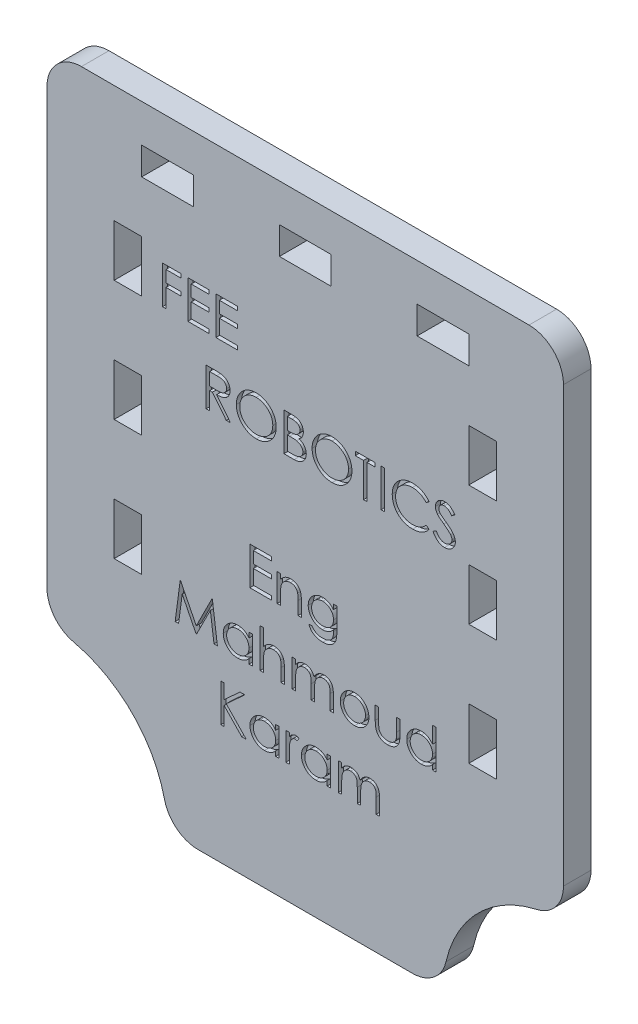
SolidWorks part; units mm, degrees
material "Beech"
ref_plane "Front" through (0, 0, 0) normal (0, 0, 1) x (1, 0, 0)
ref_plane "Top" through (0, 0, 0) normal (0, 1, 0) x (1, 0, 0)
ref_plane "Right" through (0, 0, 0) normal (1, 0, 0) x (0, 0, -1)
sketch "Sketch1" plane through (0, 0, 0) normal (0, 0, 1) x (1, 0, 0)
  line L0 (75, -55) -> (-75, -55) construction
  line L1 (-75, -90) -> (75, -90) construction
  line L2 (-75, -90) -> (-75, 90) construction
  line L3 (-75, 90) -> (75, 90) construction
  line L4 (75, -90) -> (75, 90) construction
  line L5 (-75, -90) -> (75, 90) construction
  line L6 (-75, 90) -> (75, -90) construction
  line L7 (-65, 90) -> (65, 90)
  line L8 (31.1252, -90) -> (-31.1252, -90)
  line L9 (75, -46.1252) -> (75, 80) construction
  line L10 (65, 90) -> (-65, 90) construction
  line L12 (-31.1252, -90) -> (31.1252, -90) construction
  line L17 (75, 80) -> (75, -46.1252)
  line L20 (-75, -46.1252) -> (-75, 80)
  arc A0 (-67.2222, -55.8751) -> (-40.8751, -82.2222) centre (-75, -90) cw
  arc A1 (67.2222, -55.8751) -> (40.8751, -82.2222) centre (75, -90) ccw
  arc A2 (-31.1252, -90) -> (-40.8751, -82.2222) centre (-31.1252, -80) cw
  arc A3 (-67.2222, -55.8751) -> (-75, -46.1252) centre (-65, -46.1252) cw
  arc A4 (40.8751, -82.2222) -> (31.1252, -90) centre (31.1252, -80) cw
  arc A5 (75, 80) -> (65, 90) centre (65, 80) ccw
  arc A6 (-65, 90) -> (-75, 80) centre (-65, 80) ccw
  arc A7 (75, -46.1252) -> (67.2222, -55.8751) centre (65, -46.1252) cw
  point P0 (0, 0)
  dimension "D6" = 35
  dimension "D8" = 10
  dimension "D5" = 10
  dimension "D1" = 126.1252
  dimension "D2" = 150
  dimension "D4" = 35
extrude "Boss-Extrude1" add sketch "Sketch1" along normal blind 8 contours A1 L9 L10 A0 L12 region at (0, 5.8065, 0)
sketch "Sketch2" plane through (0, 0, 8) normal (0, 0, 1) x (1, 0, 0)
  text T0 "FEE\r\n   ROBOTICS\r\n \r\n      Eng\r\n Mahmoud\r\n    Karam" font "Century Gothic" height 11
extrude "Cut-Extrude1" cut sketch "Sketch2" against normal blind 1.5
sketch "Sketch4" plane through (0, 0, 8) normal (0, 0, 1) x (1, 0, 0)
  line L0 (7.5, 71) -> (-7.5, 71)
  line L1 (-47.5, 79) -> (-32.5, 79)
  line L2 (-47.5, 79) -> (-47.5, 71)
  line L3 (-47.5, 71) -> (-32.5, 71)
  line L4 (-32.5, 79) -> (-32.5, 71)
  line L5 (-47.5, 79) -> (-32.5, 71) construction
  line L6 (-47.5, 71) -> (-32.5, 79) construction
  line L7 (-7.5, 71) -> (-7.5, 79)
  line L8 (-7.5, 79) -> (7.5, 79)
  line L9 (0, 79) -> (0, 71) construction
  line L10 (-65, 90) -> (65, 90) construction
  line L11 (47.5, 79) -> (32.5, 79)
  line L12 (47.5, 79) -> (47.5, 71)
  line L13 (47.5, 71) -> (32.5, 71)
  line L14 (32.5, 79) -> (32.5, 71)
  line L15 (7.5, 71) -> (7.5, 79)
  point P4 (-40, 75)
  dimension "D1" = 15
  dimension "D2" = 8
  dimension "D3" = 7.5
  dimension "D4" = 11
  dimension "D5" = 25
extrude "Cut-Extrude2" cut sketch "Sketch4" against normal through all
sketch "Sketch5" plane through (0, 0, 8) normal (0, 0, 1) x (1, 0, 0)
  line L0 (0, 0) -> (0, 12.759) construction
  line L1 (-47.5, 56) -> (-55.5, 56)
  line L2 (-47.5, 56) -> (-47.5, 41)
  line L3 (-47.5, 41) -> (-55.5, 41)
  line L4 (-55.5, 56) -> (-55.5, 41)
  line L5 (-47.5, 56) -> (-55.5, 41) construction
  line L6 (-47.5, 41) -> (-55.5, 56) construction
  line L7 (-47.5, 71) -> (-32.5, 71) construction
  line L8 (-47.5, 79) -> (-47.5, 71) construction
  line L9 (-47.5, 6) -> (-55.5, 6)
  line L10 (-55.5, 21) -> (-55.5, 6)
  line L11 (-47.5, 21) -> (-55.5, 21)
  line L12 (-47.5, 21) -> (-47.5, 6)
  line L13 (-47.5, -29) -> (-55.5, -29)
  line L14 (-55.5, -14) -> (-55.5, -29)
  line L15 (-47.5, -14) -> (-55.5, -14)
  line L16 (-47.5, -14) -> (-47.5, -29)
  line L17 (47.5, 41) -> (55.5, 41)
  line L18 (55.5, 56) -> (55.5, 41)
  line L19 (47.5, 56) -> (55.5, 56)
  line L20 (47.5, 56) -> (47.5, 41)
  line L21 (47.5, -14) -> (47.5, -29)
  line L22 (47.5, -14) -> (55.5, -14)
  line L23 (55.5, -14) -> (55.5, -29)
  line L24 (47.5, -29) -> (55.5, -29)
  line L25 (47.5, 21) -> (47.5, 6)
  line L26 (47.5, 21) -> (55.5, 21)
  line L27 (55.5, 21) -> (55.5, 6)
  line L28 (47.5, 6) -> (55.5, 6)
  line L29 (47.5, 71) -> (47.5, 79) construction
  point P4 (-51.5, 48.5)
  dimension "D1" = 8
  dimension "D2" = 15
  dimension "D3" = 15
  dimension "D5" = 20
  dimension "D4" = 3
extrude "Cut-Extrude3" cut sketch "Sketch5" against normal through all
